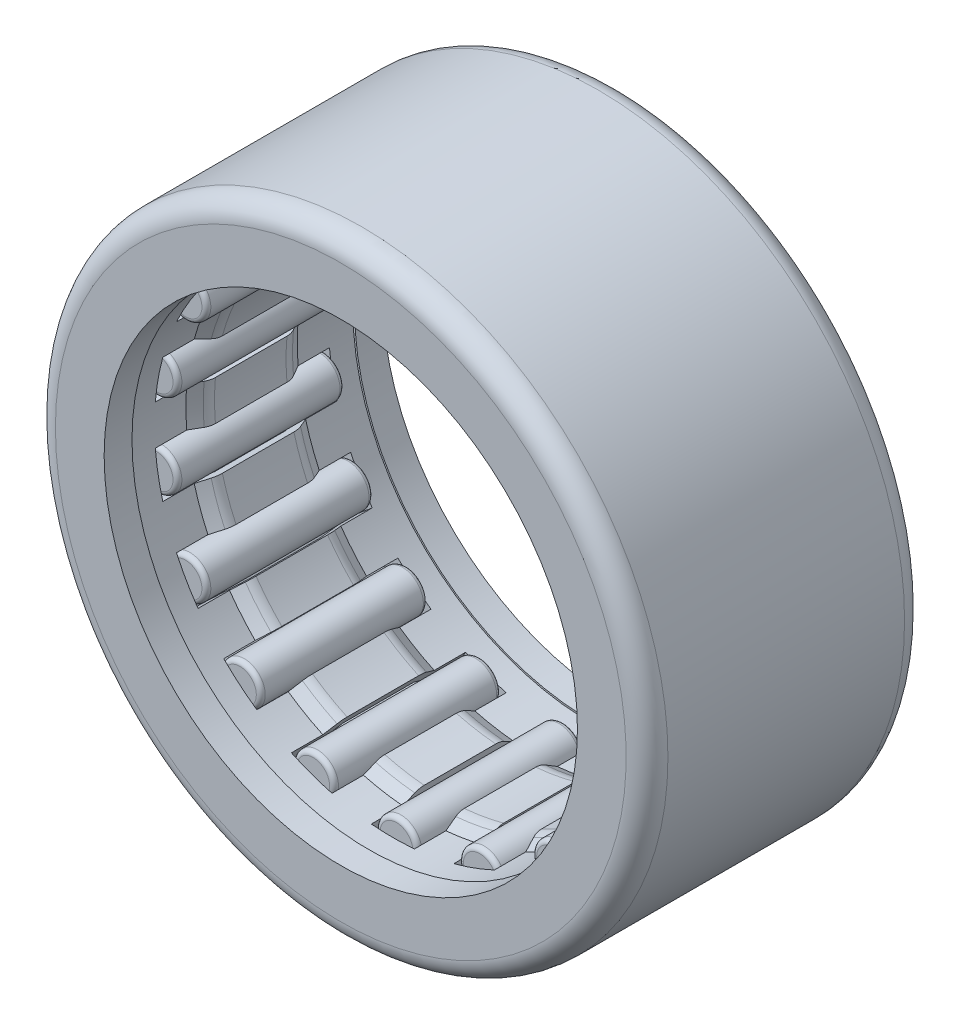
SolidWorks part; units mm, degrees
ref_plane "Front Plane" through (0, 0, 0) normal (0, 0, 1) x (1, 0, 0)
ref_plane "Top Plane" through (0, 0, 0) normal (0, 1, 0) x (1, 0, 0)
ref_plane "Right Plane" through (0, 0, 0) normal (1, 0, 0) x (0, 0, -1)
sketch "Sketch1" plane through (0, 0, 0) normal (0, 0, 1) x (1, 0, 0)
  circle A0 centre (0, 0) radius 6.35
  circle A1 centre (0, 0) radius 8.7312
  dimension "OD" = 17.4625
  dimension "ID" = 12.7
sketch "Sketch2" plane through (0, 0, 0) normal (1, 0, 0) x (0, 0, -1)
  line L0 (-3.9687, 0) -> (3.9687, 0) construction
  line L2 (-3.9688, -6.35) -> (-3.9688, 6.35) construction
  line L3 (3.9688, 8.7312) -> (-3.9688, 8.7312) construction
  line L11 (0, 0) -> (0, 8.7312) construction
  line L16 (3.9687, -8.7312) -> (3.9687, 8.7312) construction
  line L17 (-3.9688, 6.35) -> (3.9688, 6.35) construction
  line L18 (-3.9688, -6.35) -> (3.9688, -6.35) construction
  point P4 (0, 0)
  point P8 (0, 8.7312)
  point P10 (-3.9687, 0)
  dimension "For Shaft Diameter" = 12.7
  dimension "Width" = 7.9375
  dimension "For Housing ID" = 17.4625
sketch "Sketch3" plane through (0, 0, 0) normal (1, 0, 0) x (0, 0, -1)
  line L0 (-3.9688, -6.35) -> (-3.9688, 6.35) construction
  line L2 (0, 8.7312) -> (0, 7.9375) construction
  line L3 (0, 7.9375) -> (0, 7.1437) construction
  line L4 (0, 7.1437) -> (0, 6.35) construction
  line L16 (3.175, 7.9375) -> (3.175, 6.7469)
  line L17 (3.175, 6.7469) -> (3.9688, 6.7469)
  line L18 (3.9688, 6.7469) -> (3.9688, 8.7312)
  line L19 (3.9688, 8.7312) -> (-3.9688, 8.7312)
  line L20 (-3.9688, 8.7312) -> (-3.9688, 6.7469)
  line L21 (-3.9688, 6.7469) -> (-3.175, 6.7469)
  line L22 (-3.175, 6.7469) -> (-3.175, 7.9375)
  line L23 (-3.175, 7.9375) -> (3.175, 7.9375)
  point P17 (0, 6.7469)
  dimension "D1" = 6.35
revolve "Revolve1" add sketch "Sketch3" angle 360 about L0
fillet "Fillet1" radius 0.5953 2 edges at (8.7312, 0, -3.9688) (8.7312, 0, 3.9688)
sketch "Sketch4" plane through (0, 0, 0) normal (1, 0, 0) x (0, 0, -1)
  line L0 (0, 7.5406) -> (0, 6.9453) construction
  line L2 (-3.9688, 6.7469) -> (-3.175, 6.7469) construction
  line L3 (-2.3812, 6.35) -> (2.3812, 6.35)
  line L4 (-2.3812, 6.35) -> (-2.3812, 6.9453)
  line L5 (-2.3812, 6.9453) -> (2.3812, 6.9453)
  line L6 (2.3812, 6.35) -> (2.3812, 6.9453)
  line L7 (0, 7.9375) -> (0, 7.1437) construction
  line L8 (-2.3812, 6.6477) -> (2.3812, 6.6477) construction
  line L9 (-3.175, 6.7469) -> (-2.3812, 6.7469) construction
  point P15 (2.4828, 6.7469)
  point P16 (-2.4828, 6.7469)
  dimension "D1" = 0.1016
revolve "Revolve2" add sketch "Sketch4" angle 360 about L5
fillet "Fillet2" radius 0.127 2 edges at (0, 6.35, 2.3812) (0, 6.35, -2.3812)
sketch "Sketch5" plane through (0, 0, 0) normal (0, 0, 1) x (1, 0, 0)
  line L0 (0, 0) -> (0.5953, 6.9453) construction
  line L1 (0, -6.35) -> (0, 6.35) construction
  line L2 (0.5953, 6.9453) -> (-0.5953, 6.9453) construction
  line L3 (-0.5953, 6.9453) -> (0, 0) construction
  circle A0 centre (0, 6.9453) radius 0.5953
  circle A1 centre (0, 6.9453) radius 0.5953
  dimension "D1" = 9.798
pattern_circular "CirPattern1" count 18 over 360 about axis through (0, 0, 3.9687) along (0, 0, -1) of bodies 105
sketch "Sketch6" plane through (0, 0, 0) normal (1, 0, 0) x (0, 0, -1)
  line L0 (0, 6.7469) -> (0, 7.1437) construction
  line L1 (-3.175, 6.7977) -> (3.175, 6.7977) construction
  line L2 (-3.175, 6.7977) -> (-3.175, 7.3422)
  line L3 (-3.175, 7.3422) -> (-1.955, 7.3422) construction
  line L5 (-3.175, 6.7977) -> (-1.5875, 6.7977)
  line L6 (-1.5875, 6.7977) -> (-1.1558, 6.5484)
  line L7 (-1.1558, 6.5484) -> (1.1558, 6.5484)
  line L8 (3.175, 7.9375) -> (3.175, 6.7469) construction
  line L9 (-3.175, 6.7469) -> (-3.175, 7.9375) construction
  line L10 (-3.9688, 6.7469) -> (-3.175, 6.7469) construction
  line L13 (0, 6.35) -> (0, 6.7469) construction
  line L14 (0, 7.1437) -> (0, 6.35) construction
  line L15 (1.5875, 6.7977) -> (1.1558, 6.5484)
  line L16 (-3.175, 7.3422) -> (-1.955, 7.3422)
  line L17 (-1.955, 7.3422) -> (-1.0119, 6.7977)
  line L18 (-1.0119, 6.7977) -> (1.0119, 6.7977)
  line L21 (-1.1558, 6.5484) -> (-1.0119, 6.7977) construction
  line L22 (3.175, 6.7977) -> (1.5875, 6.7977)
  line L23 (3.175, 6.7977) -> (3.175, 7.3422)
  line L24 (3.175, 7.3422) -> (1.955, 7.3422)
  line L25 (1.955, 7.3422) -> (1.0119, 6.7977)
  line L26 (0, 6.35) -> (-0.7937, 6.35) construction
  line L29 (-2.3812, 6.35) -> (2.3812, 6.35) construction
  line L30 (-0.7937, 6.35) -> (-1.5875, 6.35) construction
  line L31 (-1.5875, 6.35) -> (-2.3812, 6.35) construction
  point P10 (0, 6.5484)
  point P18 (0, 6.7469)
  point P24 (0, 6.5484)
  point P28 (0, 6.7977)
  dimension "D1" = 0.0508
  dimension "D2" = 30
revolve "Revolve3" add sketch "Sketch6" angle 360 about L0
fillet "Fillet3" radius 0.508 2 edges at (6.5484, 0, 1.1558) (6.5484, 0, -1.1558)
sketch "Sketch7" plane through (0, 0, 0) normal (0, 0, 1) x (1, 0, 0)
  line L0 (0, 6.35) -> (0, 6.9453) construction
  line L1 (0, 6.35) -> (0, 6.9453) construction
  line L3 (-0.5322, 6.2992) -> (0.5322, 6.2992)
  line L4 (-0.5322, 6.2992) -> (-0.76, 7.5914)
  line L5 (-0.76, 7.5914) -> (0.76, 7.5914)
  line L6 (0.5322, 6.2992) -> (0.76, 7.5914)
  line L7 (0, 7.5914) -> (0, 6.2992) construction
  line L8 (-0.6461, 6.9453) -> (0.6461, 6.9453) construction
  circle A0 centre (0, 6.9453) radius 0.5953 construction
  circle A1 centre (0, 6.9453) radius 0.6461 construction
  dimension "D2" = 20
  dimension "D1" = 0.0508
extrude "Cut-Extrude1" cut sketch "Sketch7" along normal up to vertex (2.4829 mm away) and the other way up to vertex (2.4829 mm away) up to point (0, 6.7469, 2.4828) other way up to point (0, 6.7469, -2.4828)
pattern_circular "CirPattern2" count 18 over 360 about axis through (0, 0, 3.9687) along (0, 0, -1) of "Cut-Extrude1"
equation "\"D1@Fillet1\" =  ( \"OD@Sketch1\" - \"For Shaft Diameter@Sketch2\" )  * .125"
equation "\"D1@CirPattern1\" = 360 / \"D1@Sketch5\" / 2"
equation "\"D2\"= \"D1\""
equation "\"D1@CirPattern2\" = \"D1@CirPattern1\""
equation "\"D1@Sketch3\" = \"Width@Sketch2\" * .8"
